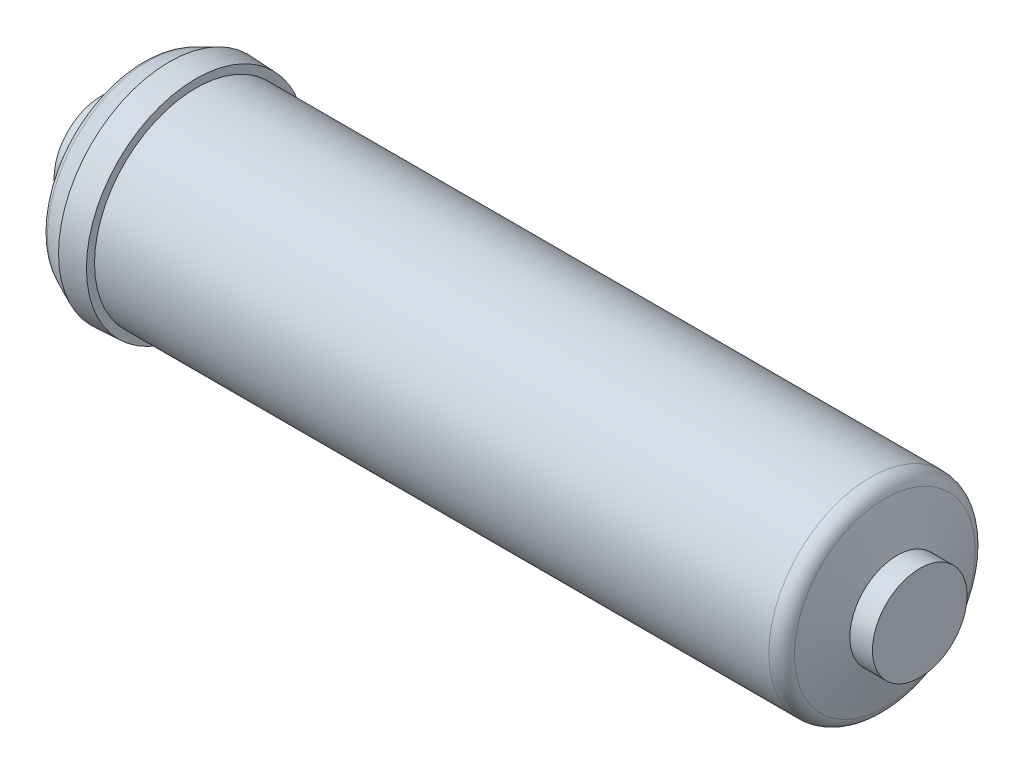
SolidWorks part; units mm, degrees
ref_plane "Front Plane" through (0, 0, 0) normal (0, 0, 1) x (1, 0, 0)
ref_plane "Top Plane" through (0, 0, 0) normal (0, 1, 0) x (1, 0, 0)
ref_plane "Right Plane" through (0, 0, 0) normal (1, 0, 0) x (0, 0, -1)
sketch "Sketch1" plane through (0, 0, 0) normal (0, 0, 1) x (1, 0, 0)
  line L1 (257.175, 0) -> (257.175, 14.859)
  line L2 (257.175, 14.859) -> (250.063, 14.859)
  line L3 (250.063, 14.859) -> (245.237, 31.877)
  line L4 (245.237, 31.877) -> (29.718, 31.877)
  line L5 (29.718, 31.877) -> (29.718, 34.417)
  line L6 (29.718, 34.417) -> (21.336, 34.798)
  line L7 (21.336, 34.798) -> (12.954, 30.988)
  line L8 (12.954, 30.988) -> (7.9502, 14.859)
  line L9 (7.9502, 14.859) -> (0, 14.859)
  line L10 (0, 14.859) -> (0, 0)
  line L11 (0, 0) -> (257.175, 0) construction
  line L12 (0, 0) -> (257.175, 0)
  point P8 (17.7126, 30.2376)
  point P13 (24.792, 34.798)
  point P14 (14.1728, 30.8931)
  point P15 (29.718, 33.9084)
  point P16 (236.0368, 31.877)
  point P17 (241.3984, 31.877)
  dimension "D1" = 257.175
  dimension "D2" = 29.718
  dimension "D3" = 7.9502
  dimension "D4" = 7.112
  dimension "D5" = 69.596
  dimension "D6" = 29.718
  dimension "D7" = 63.754
  dimension "D8" = 2.54
  dimension "D9" = 8.382
  dimension "D10" = 8.382
  dimension "D11" = 61.976
  dimension "D12" = 11.938
revolve "Revolve1" add sketch "Sketch1" angle 360 about L11
fillet "Fillet1" radius 4.7625 2 edges at (12.954, 0, 30.988) (245.237, 0, 31.877)
